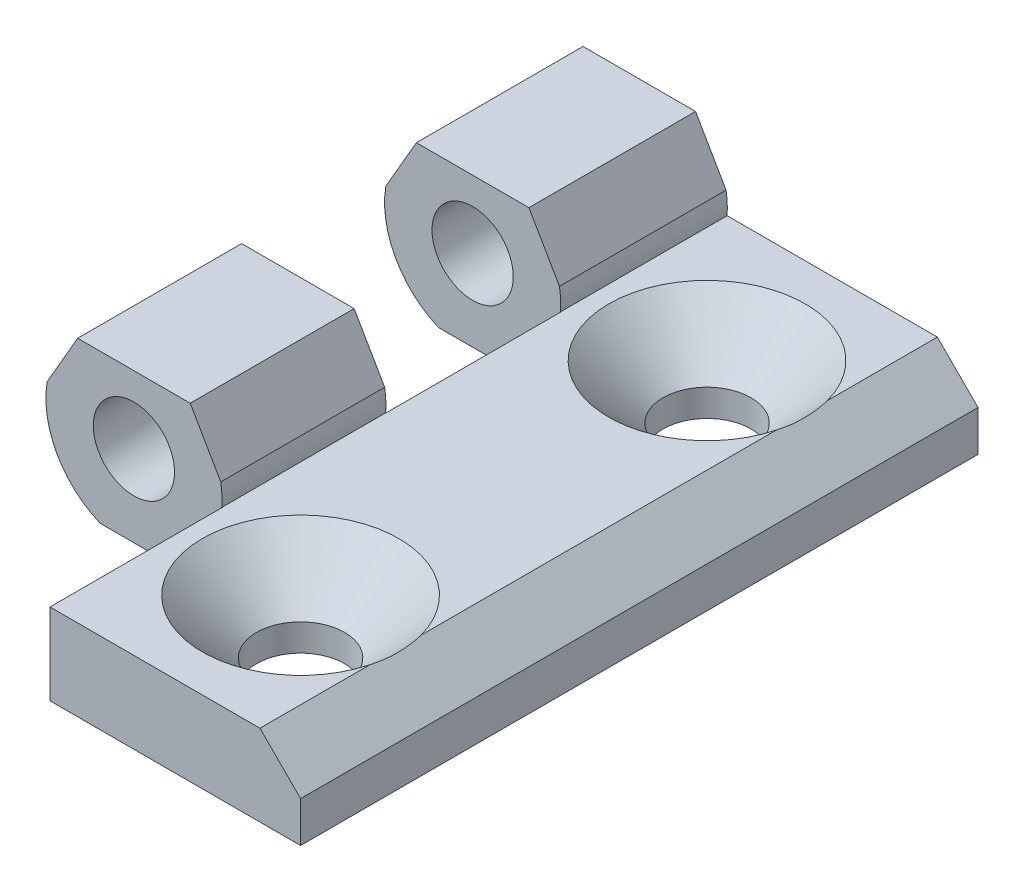
SolidWorks part; units mm, degrees
material "AISI 1020"
ref_plane "Front Plane" through (0, 0, 0) normal (0, 0, 1) x (1, 0, 0)
ref_plane "Top Plane" through (0, 0, 0) normal (0, 1, 0) x (1, 0, 0)
ref_plane "Right Plane" through (0, 0, 0) normal (1, 0, 0) x (0, 0, -1)
sketch "Sketch2" plane through (0, 0, 0) normal (0, 0, 1) x (1, 0, 0)
  line L0 (25, -6.5) -> (2, -6.5)
  line L1 (2, -6.5) -> (2, -6)
  line L2 (25, -6.5) -> (25, -3.5)
  line L3 (25, -3.5) -> (22, -0.5)
  line L4 (22, -0.5) -> (6.4807, -0.5)
  line L5 (-4.1533, 5) -> (4.1533, 5)
  line L6 (2, -6) -> (-2.5, -6)
  circle A0 centre (0, 0) radius 3
  arc A1 (-4.1533, 5) -> (-2.5, -6) centre (0, 0) ccw
  arc A2 (6.4807, -0.5) -> (4.1533, 5) centre (0, 0) ccw
  dimension "D1" = 6
  dimension "D7" = 6.5
  dimension "D2" = 6
  dimension "D3" = 11.5
  dimension "D4" = 25
  dimension "D5" = 45
  dimension "D6" = 6.5
  dimension "D8" = 0.5
  dimension "D9" = 23
  dimension "D10" = 3
extrude "Boss-Extrude1" add sketch "Sketch2" along normal mid plane 50
sketch "Sketch3" plane through (0, -0.5, 0) normal (0, 1, 0) x (1, 0, 0)
  line L0 (15, 15) -> (15, -15) construction
  circle A0 centre (15, 15) radius 3.25
  circle A1 centre (15, -15) radius 3.25
  point P4 (15, 0)
  dimension "D1" = 30
  dimension "D2" = 15
  dimension "D3" = 6.5
extrude "Cut-Extrude1" cut sketch "Sketch3" against normal through all
chamfer "Chamfer1" distance 4 angle 45 2 edges at (11.75, -0.5, 15) (11.75, -0.5, -15)
sketch "Sketch4" plane through (0, 0, 25) normal (0, 0, 1) x (1, 0, 0)
  line L0 (6.4068, 1.0969) -> (4.1533, 5)
  line L1 (-4.1533, 5) -> (-6.4068, 1.0969)
  line L3 (4.1533, 5) -> (-4.1533, 5) construction
  arc A0 (6.4807, -0.5) -> (4.1533, 5) centre (0, 0) ccw construction
  arc A1 (-4.1533, 5) -> (-2.5, -6) centre (0, 0) ccw construction
  arc A2 (-6.4068, 1.0969) -> (-4.1533, 5) centre (0, 0) cw
  arc A3 (4.1533, 5) -> (6.4068, 1.0969) centre (0, 0) cw
  dimension "D1" = 60
extrude "Cut-Extrude2" cut sketch "Sketch4" against normal through all
sketch "Sketch5" plane through (0, 5, 0) normal (0, 1, 0) x (1, 0, 0)
  line L0 (6.5, -25) -> (6.5, 25) construction
  line L1 (-6.5, -25) -> (6.5, -25)
  line L2 (-6.5, -25) -> (-6.5, -12.5)
  line L3 (-6.5, -12.5) -> (6.5, -12.5)
  line L4 (6.5, -25) -> (6.5, -12.5)
  line L6 (-6.5, 12.5) -> (6.5, 12.5)
  line L7 (-6.5, 12.5) -> (-6.5, 0)
  line L8 (-6.5, 0) -> (6.5, 0)
  line L9 (6.5, 12.5) -> (6.5, 0)
  line L10 (-6.5, 25) -> (-6.5, -25) construction
  line L11 (0, -12.5) -> (0, 0) construction
  line L12 (0, 0) -> (0, 12.5) construction
  line L13 (0, 12.5) -> (0, 25) construction
  line L14 (4.1533, 25) -> (-4.1533, 25) construction
  line L15 (0, -12.5) -> (0, -25) construction
extrude "Cut-Extrude3" cut sketch "Sketch5" against normal through all
sketch "Sketch6" plane through (0, 5, 0) normal (0, 1, 0) x (1, 0, 0)
  line L0 (-6.5, 0) -> (-6.5, -12.5) construction
  line L1 (6.5, 0) -> (-6.5, 0)
  line L2 (6.5, 0) -> (6.5, -0.2)
  line L3 (6.5, -0.2) -> (-6.5, -0.2)
  line L4 (-6.5, 0) -> (-6.5, -0.2)
  line L5 (-6.5, 25) -> (-6.5, 12.5) construction
  line L6 (6.5, -12.5) -> (-6.5, -12.5)
  line L7 (6.5, -12.5) -> (6.5, -12.3)
  line L8 (6.5, -12.3) -> (-6.5, -12.3)
  line L9 (-6.5, -12.5) -> (-6.5, -12.3)
  line L10 (6.5, 12.5) -> (-6.5, 12.5)
  line L11 (6.5, 12.5) -> (6.5, 12.7)
  line L12 (6.5, 12.7) -> (-6.5, 12.7)
  line L13 (-6.5, 12.5) -> (-6.5, 12.7)
  dimension "D1" = 0.2
  dimension "D2" = 0.2
  dimension "D3" = 0.2
extrude "Cut-Extrude4" cut sketch "Sketch6" against normal through all
